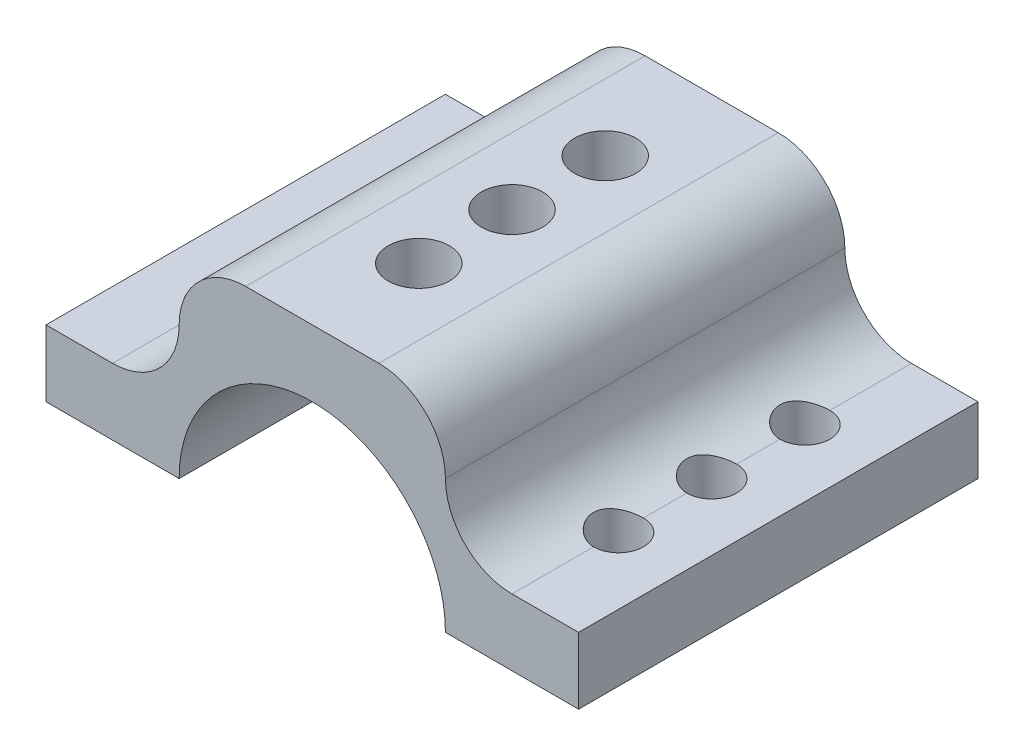
SolidWorks part; units mm, degrees
ref_plane "Front Plane" through (0, 0, 0) normal (0, 0, 1) x (1, 0, 0)
ref_plane "Top Plane" through (0, 0, 0) normal (0, 1, 0) x (1, 0, 0)
ref_plane "Right Plane" through (0, 0, 0) normal (1, 0, 0) x (0, 0, -1)
sketch "Sketch1" plane through (0, 0, 0) normal (0, 1, 0) x (1, 0, 0)
  line L7 (-34.629, 17.5668) -> (16.171, 17.5668)
  line L8 (-34.629, 17.5668) -> (-34.629, -20.5332)
  line L9 (-34.629, -20.5332) -> (16.171, -20.5332)
  line L10 (16.171, 17.5668) -> (16.171, -20.5332)
  circle A6 centre (-28.279, 7.4068) radius 2.3813
  circle A7 centre (-28.279, -1.4832) radius 2.3813
  circle A8 centre (-28.279, -10.3732) radius 2.3813
  circle A9 centre (9.821, -10.3732) radius 2.3813
  circle A10 centre (9.821, -1.4832) radius 2.3812
  circle A11 centre (9.821, 7.4068) radius 2.3813
  dimension "D4" = 8.89
  dimension "D6" = 8.89
  dimension "D7" = 50.8
  dimension "D8" = 38.1
  dimension "D9" = 19.05
  dimension "D10" = 6.35
extrude "Boss-Extrude1" add sketch "Sketch1" along normal blind 25.4
sketch "Sketch2" plane through (0, 0, 20.5332) normal (0, 0, 1) x (1, 0, 0)
  line L0 (-34.629, 0) -> (16.171, 0) construction
  line L1 (-21.929, 0) -> (3.471, 0)
  line L3 (-25.739, 25.4) -> (7.281, 25.4)
  line L4 (-34.629, 25.4) -> (-25.739, 25.4)
  line L5 (-34.629, 25.4) -> (-34.629, 6.35)
  line L6 (-34.629, 6.35) -> (-21.929, 6.35)
  line L8 (16.171, 25.4) -> (7.281, 25.4)
  line L9 (16.171, 25.4) -> (16.171, 6.35)
  line L10 (16.171, 6.35) -> (3.471, 6.35)
  line L12 (-21.929, 6.35) -> (-21.929, 19.05)
  line L13 (-21.929, 19.05) -> (3.471, 19.05)
  line L14 (3.471, 19.05) -> (3.471, 6.35)
  arc A0 (3.471, 0) -> (-21.929, 0) centre (-9.229, 0) ccw
  dimension "D1" = 12.7
  dimension "D4" = 19.05
  dimension "D2" = 12.7
  dimension "D3" = 6.35
extrude "Cut-Extrude1" cut sketch "Sketch2" against normal through all
fillet "Fillet1" radius 6.35 4 edges at (3.471, 6.35, 1.4832) (3.471, 19.05, 1.4832) (-21.929, 6.35, 1.4832) (-21.929, 19.05, 1.4832)
sketch "Sketch3" plane through (0, 19.05, 0) normal (0, 1, 0) x (1, 0, 0)
  line L0 (-15.579, 17.5668) -> (-2.879, 17.5668) construction
  line L1 (-34.629, 17.5668) -> (-34.629, -20.5332) construction
  circle A0 centre (-9.229, -1.4832) radius 2.921
  circle A2 centre (-9.229, 7.4068) radius 2.921
  circle A3 centre (-9.229, -10.3732) radius 2.921
  dimension "D1" = 19.05
  dimension "D3" = 5.842
  dimension "D5" = 8.89
  dimension "D4" = 8.89
  dimension "D2" = 25.4
extrude "Cut-Extrude2" cut sketch "Sketch3" against normal blind 25.4
